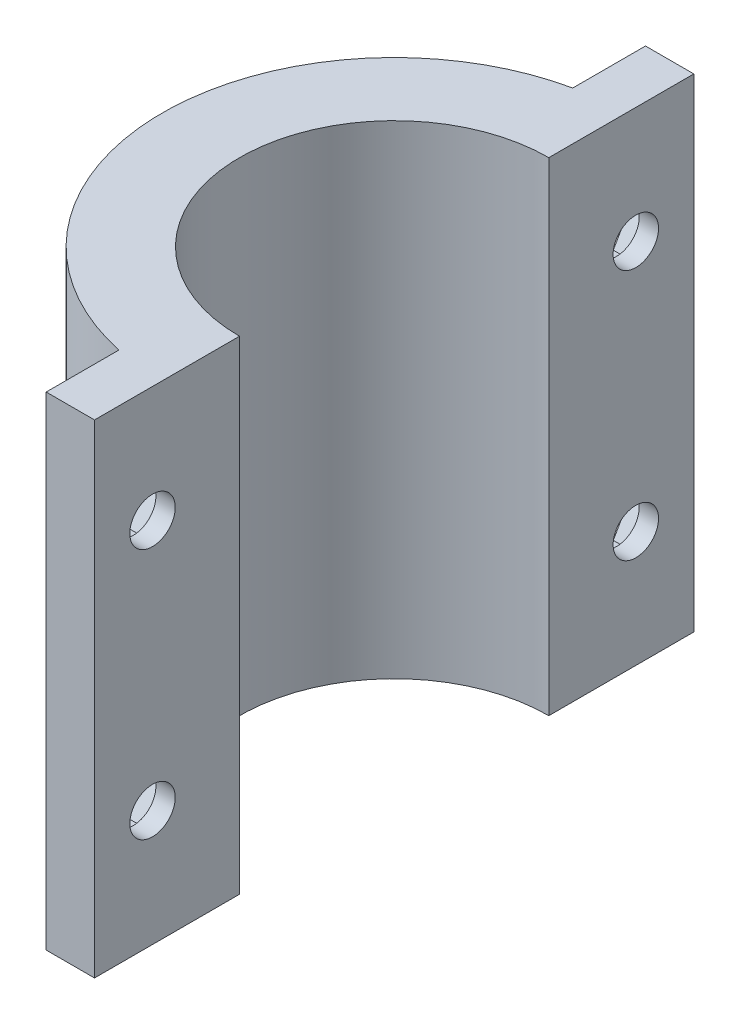
SolidWorks part; units mm, degrees
ref_plane "Front Plane" through (0, 0, 0) normal (0, 0, 1) x (1, 0, 0)
ref_plane "Top Plane" through (0, 0, 0) normal (0, 1, 0) x (1, 0, 0)
ref_plane "Right Plane" through (0, 0, 0) normal (1, 0, 0) x (0, 0, -1)
sketch "Sketch1" plane through (0, 0, 0) normal (0, 1, 0) x (1, 0, 0)
  line L1 (0, -16) -> (0, -31)
  line L2 (-5, -31) -> (0, -31)
  line L4 (0, 16) -> (0, 31)
  line L5 (0, 31) -> (-5, 31)
  line L6 (-5, 23.4734) -> (-5, 31)
  line L10 (-5, -23.4734) -> (-5, -31)
  arc A0 (-5, 23.4734) -> (-5, -23.4734) centre (0, 0) ccw
  arc A1 (0, 16) -> (0, -16) centre (0, 0) ccw
  dimension "D3" = 8
  dimension "D1" = 32
  dimension "D2" = 5
  dimension "D4" = 15
  dimension "D5" = 15
extrude "Boss-Extrude1" add sketch "Sketch1" along normal blind 50
sketch "Sketch2" plane through (-5, 0, 0) normal (-1, 0, 0) x (0, 0, 1)
  line L0 (-31, 50) -> (-23.4734, 50) construction
  line L1 (-22.3298, 33.375) -> (-19.6595, 38)
  line L2 (-19.6595, 38) -> (-22.3298, 42.625)
  line L3 (-22.3298, 42.625) -> (-27.6702, 42.625)
  line L4 (-27.6702, 42.625) -> (-30.3405, 38)
  line L5 (-30.3405, 38) -> (-27.6702, 33.375)
  line L6 (-27.6702, 33.375) -> (-22.3298, 33.375)
  line L13 (-31, 0) -> (-23.4734, 0) construction
  line L14 (-22.3298, 7.375) -> (-19.6595, 12)
  line L15 (-19.6595, 12) -> (-22.3298, 16.625)
  line L16 (-22.3298, 16.625) -> (-27.6702, 16.625)
  line L17 (-27.6702, 16.625) -> (-30.3405, 12)
  line L18 (-30.3405, 12) -> (-27.6702, 7.375)
  line L19 (-27.6702, 7.375) -> (-22.3298, 7.375)
  line L22 (0, -13.2) -> (0, 13.2) construction
  line L23 (27.6702, 7.375) -> (22.3298, 7.375)
  line L24 (22.3298, 7.375) -> (19.6595, 12)
  line L25 (19.6595, 12) -> (22.3298, 16.625)
  line L26 (27.6702, 16.625) -> (30.3405, 12)
  line L27 (30.3405, 12) -> (27.6702, 7.375)
  line L28 (22.3298, 16.625) -> (27.6702, 16.625)
  line L29 (27.6702, 42.625) -> (30.3405, 38)
  line L30 (27.6702, 33.375) -> (22.3298, 33.375)
  line L31 (22.3298, 33.375) -> (19.6595, 38)
  line L32 (19.6595, 38) -> (22.3298, 42.625)
  line L33 (22.3298, 42.625) -> (27.6702, 42.625)
  line L34 (30.3405, 38) -> (27.6702, 33.375)
  line L36 (-31, 50) -> (-31, 0) construction
  circle A0 centre (-25, 38) radius 4.625 construction
  circle A1 centre (-25, 12) radius 4.625 construction
  circle A2 centre (25, 12) radius 4.625 construction
  circle A3 centre (25, 38) radius 4.625 construction
  circle A4 centre (-25, 38) radius 2.35
  circle A5 centre (-25, 12) radius 2.35
  circle A6 centre (25, 12) radius 2.35
  circle A7 centre (25, 38) radius 2.35
  line M4 (-23.4734, 0) -> (-23.4734, 50)
  dimension "D5" = 4.7
  dimension "D6" = 4.7
  dimension "D1" = 9.25
  dimension "D2" = 12
  dimension "D3" = 12
  dimension "D4" = 9.25
  dimension "D7" = 6
extrude "Cut-Extrude1" cut sketch "Sketch2" along normal blind 50 contours L1 L2 L3 L4 L5 L6 | L14 L15 L16 L17 L18 L19 | L23 L24 L25 L28 L26 L27 | L29 L34 L30 L31 L32 L33
extrude "Cut-Extrude5" cut sketch "Sketch2<7>" against normal blind 10 contours A4 M4 | A5 M4 | A7 | A6 | A5 | A4 region at (-5, 38, -25.2484) region at (-5, 12, -25.2484) region at (-5, 12, 25) region at (-5, 38, 25)
sketch "Sketch2<7>" plane through (-5, 0, 0) normal (-1, 0, 0) x (0, 0, 1) same geometry as "Sketch2"
extrude "Cut-Extrude8" cut sketch "Sketch2<10>" against normal blind 3
sketch "Sketch2<10>" plane through (-5, 0, 0) normal (-1, 0, 0) x (0, 0, 1) same geometry as "Sketch2"
